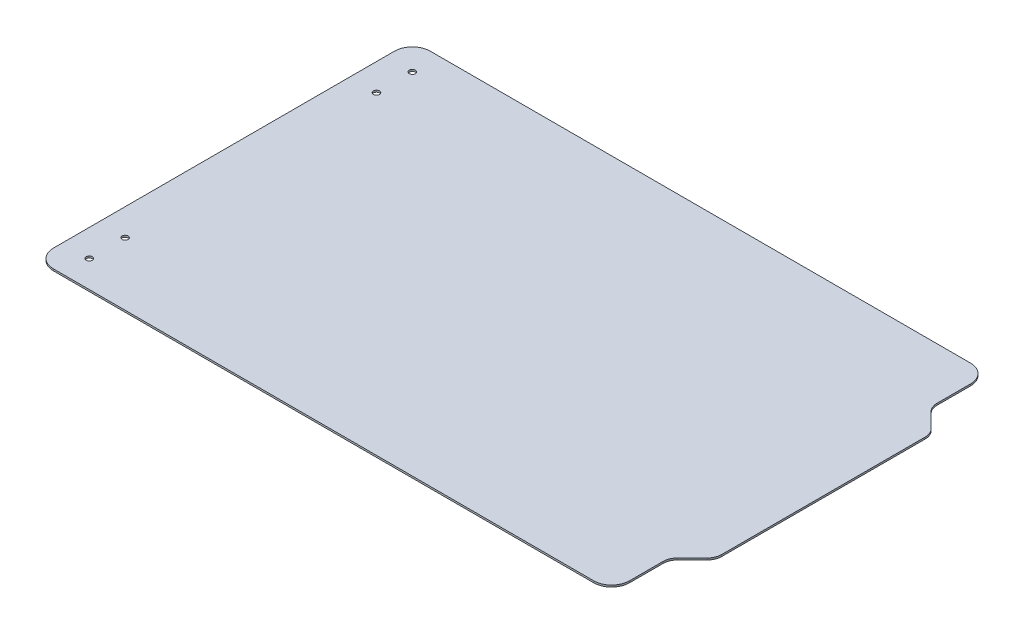
SolidWorks part; units mm, degrees
material "AISI 1020 Steel, Cold Rolled"
ref_plane "Front Plane" through (0, 0, 0) normal (0, 0, 1) x (1, 0, 0)
ref_plane "Top Plane" through (0, 0, 0) normal (0, 1, 0) x (1, 0, 0)
ref_plane "Right Plane" through (0, 0, 0) normal (1, 0, 0) x (0, 0, -1)
sketch "Sketch1" plane through (0, 0, 0) normal (0, 1, 0) x (1, 0, 0)
  line L1 (-167, 105) -> (167, 105)
  line L2 (-167, 105) -> (-167, -105)
  line L3 (-167, -105) -> (167, -105)
  line L4 (167, 105) -> (167, -105)
  line L5 (-167, 105) -> (167, -105) construction
  line L6 (-167, -105) -> (167, 105) construction
  point P0 (0, 0)
  dimension "D1" = 334
  dimension "D2" = 210
extrude "Boss-Extrude1" add sketch "Sketch1" along normal blind 1
sketch "Sketch2" plane through (0, 0, 0) normal (0, -1, 0) x (-1, 0, 0)
  line L0 (-167, -60) -> (-154, -73)
  line L5 (-167, -105) -> (-167, 105) construction
  line L6 (-154, -73) -> (-154, -105)
  line L7 (167, -105) -> (-167, -105) construction
  line L8 (-154, -105) -> (-167, -105)
  line L9 (-167, -105) -> (-167, -60)
  line L10 (-55, 0) -> (55, 0) construction
  line L11 (-154, 105) -> (-167, 105)
  line L12 (-154, 73) -> (-154, 105)
  line L13 (-167, 60) -> (-154, 73)
  line L14 (-167, 105) -> (-167, 60)
  dimension "D1" = 13
  dimension "D2" = 45
  dimension "D3" = 32
extrude "Cut-Extrude1" cut sketch "Sketch2" against normal through all
fillet "Fillet1" radius 8 4 edges at (154, 0.5, -73) (167, 0.5, -60) (154, 0.5, 73) (167, 0.5, 60)
fillet "Fillet2" radius 10 4 edges at (154, 0.5, -105) (-167, 0.5, -105) (-167, 0.5, 105) (154, 0.5, 105)
sketch "Sketch3" plane through (0, 0, 0) normal (0, -1, 0) x (1, 0, 0)
  circle A0 centre (-152, -70) radius 1.7 construction
  circle A1 centre (-152, -90) radius 1.7 construction
  circle A2 centre (-152, 70) radius 1.7 construction
  circle A3 centre (-152, 90) radius 1.7 construction
  circle A4 centre (-152, -70) radius 1.7
  circle A5 centre (-152, -90) radius 1.7
  circle A6 centre (-152, 70) radius 1.7
  circle A7 centre (-152, 90) radius 1.7
extrude "Cut-Extrude2" cut sketch "Sketch3" against normal through all
